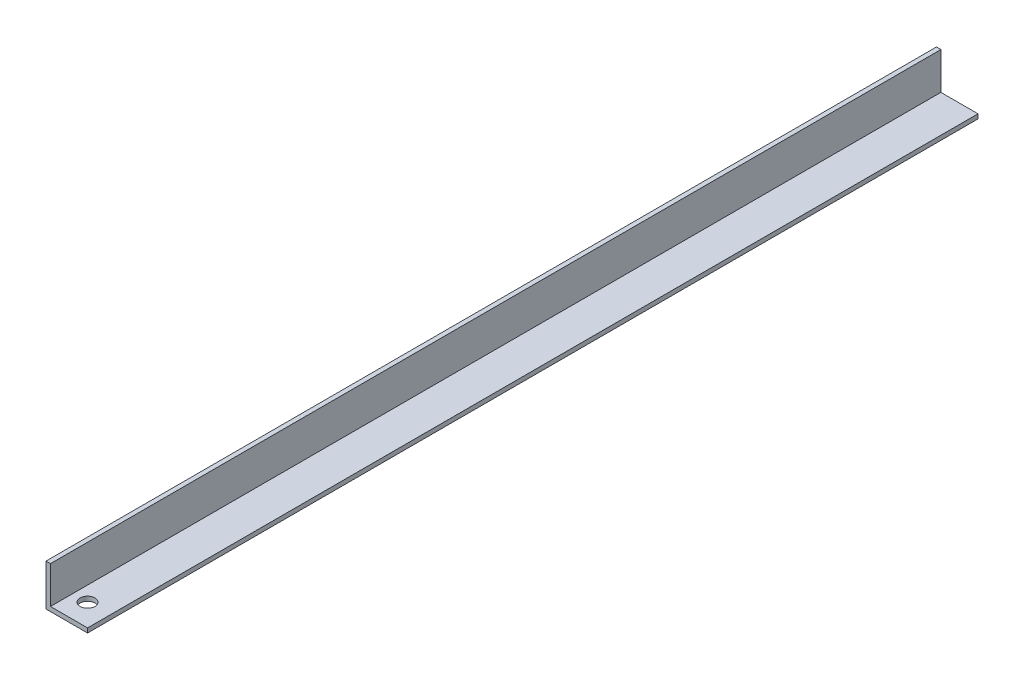
SolidWorks part; units mm, degrees
ref_plane "Спереди" through (0, 0, 0) normal (0, 0, 1) x (1, 0, 0)
ref_plane "Сверху" through (0, 0, 0) normal (0, 1, 0) x (1, 0, 0)
ref_plane "Справа" through (0, 0, 0) normal (1, 0, 0) x (0, 0, -1)
sketch "Эскиз1" plane through (0, 0, 0) normal (0, 0, 1) x (1, 0, 0)
  line L0 (0, 25) -> (0, 0)
  line L1 (0, 0) -> (25, 0)
extrude "Вытянуть-Тонкостенный1" add sketch "Эскиз1" along normal blind 600 thin thin type one direction wall 3
sketch "Эскиз2" plane through (0, -3, 0) normal (0, -1, 0) x (1, 0, 0)
  circle A0 centre (10, 585) radius 5
extrude "Вырез-Вытянуть1" cut sketch "Эскиз2" against normal blind 10
